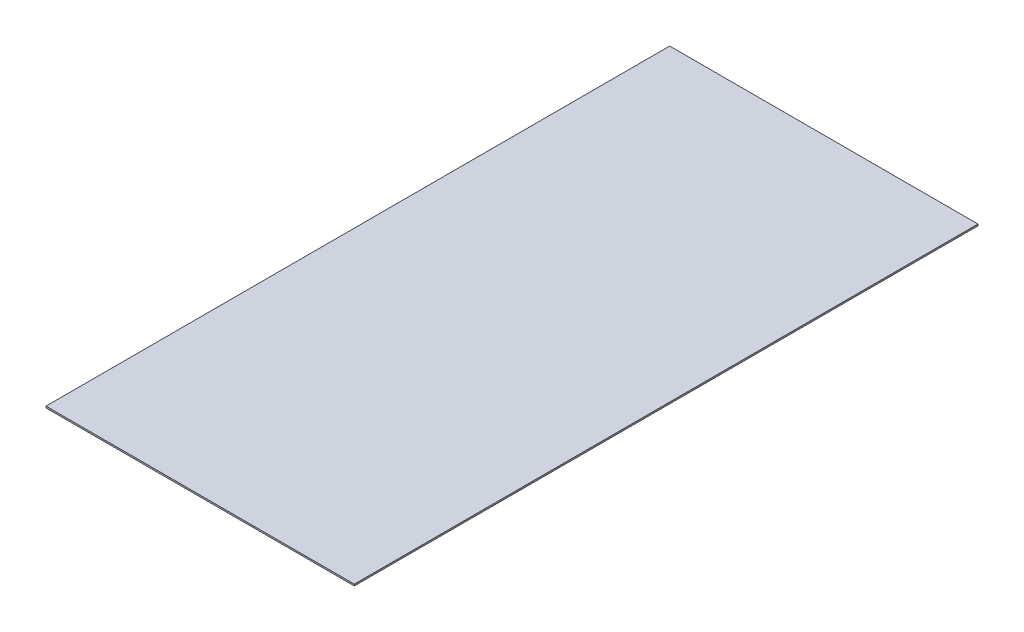
SolidWorks part; units mm, degrees
ref_plane "Front Plane" through (0, 0, 0) normal (0, 0, 1) x (1, 0, 0)
ref_plane "Top Plane" through (0, 0, 0) normal (0, 1, 0) x (1, 0, 0)
ref_plane "Right Plane" through (0, 0, 0) normal (1, 0, 0) x (0, 0, -1)
ref_axis "X-Axis" through (-88.99, 0, 0) along (1, 0, 0)
ref_axis "Y-Axis" through (0, 55, 0) along (0, -1, 0)
ref_axis "Z-Axis" through (0, 0, -88.99) along (0, 0, 1)
sketch "Sketch1" plane through (0, 0, 0) normal (0, 1, 0) x (1, 0, 0)
  line L1 (-17.5, -35.4) -> (17.5, -35.4)
  line L2 (-17.5, -35.4) -> (-17.5, 35.4)
  line L3 (-17.5, 35.4) -> (17.5, 35.4)
  line L4 (17.5, -35.4) -> (17.5, 35.4)
  line L5 (-17.5, -35.4) -> (17.5, 35.4) construction
  line L6 (-17.5, 35.4) -> (17.5, -35.4) construction
  point P0 (0, 0)
  dimension "D1" = 70.8
  dimension "D2" = 35
extrude "Boss-Extrude1" add sketch "Sketch1" along normal blind 0.18
